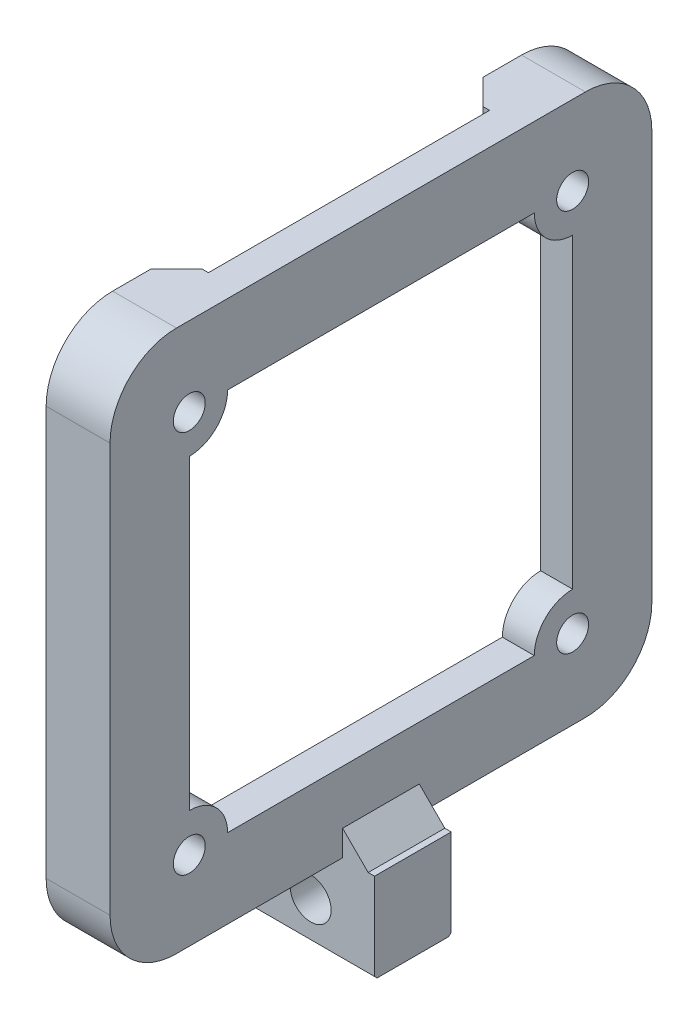
SolidWorks part; units mm, degrees
ref_plane "Front Plane" through (0, 0, 0) normal (0, 0, 1) x (1, 0, 0)
ref_plane "Top Plane" through (0, 0, 0) normal (0, 1, 0) x (1, 0, 0)
ref_plane "Right Plane" through (0, 0, 0) normal (1, 0, 0) x (0, 0, -1)
sketch "Sketch1" plane through (0, 0, 0) normal (1, 0, 0) x (0, 0, -1)
  line L0 (-23.0849, 19.7931) -> (-23.0849, -12.2069)
  line L1 (-20.0849, -15.2069) -> (11.9151, -15.2069)
  line L2 (14.9151, -12.2069) -> (14.9151, 19.7931)
  line L3 (11.9151, 22.7931) -> (-20.0849, 22.7931)
  line L4 (-19.0849, 15.7931) -> (-19.0849, -8.2069)
  line L5 (-19.0849, -11.2069) -> (-17.8349, -11.2069) construction
  line L6 (10.9151, -11.2069) -> (10.9151, -9.9569) construction
  line L7 (10.9151, 18.7931) -> (9.6651, 18.7931) construction
  line L8 (-16.0849, 18.7931) -> (-17.8349, 18.7931) construction
  line L9 (-19.0849, 18.7931) -> (-19.0849, 17.5431) construction
  line L10 (-19.0849, 18.7931) -> (-19.0849, -11.2069) construction
  line L11 (-17.8349, 18.7931) -> (-19.0849, 18.7931) construction
  line L12 (10.9151, 18.7931) -> (-19.0849, 18.7931) construction
  line L13 (-19.0849, 17.5431) -> (-19.0849, 15.7931) construction
  line L14 (7.9151, 18.7931) -> (-16.0849, 18.7931)
  line L15 (9.6651, 18.7931) -> (7.9151, 18.7931) construction
  line L16 (10.9151, 17.5431) -> (10.9151, 18.7931) construction
  line L17 (10.9151, -8.2069) -> (10.9151, 15.7931)
  line L18 (10.9151, 15.7931) -> (10.9151, 17.5431) construction
  line L19 (10.9151, -11.2069) -> (10.9151, 18.7931) construction
  line L20 (10.9151, -9.9569) -> (10.9151, -8.2069) construction
  line L21 (9.6651, -11.2069) -> (10.9151, -11.2069) construction
  line L22 (-16.0849, -11.2069) -> (7.9151, -11.2069)
  line L23 (7.9151, -11.2069) -> (9.6651, -11.2069) construction
  line L24 (-19.0849, -11.2069) -> (10.9151, -11.2069) construction
  line L25 (-17.8349, -11.2069) -> (-16.0849, -11.2069) construction
  line L26 (-19.0849, -9.9569) -> (-19.0849, -11.2069) construction
  line L27 (-19.0849, -8.2069) -> (-19.0849, -9.9569) construction
  arc A0 (-17.8349, 18.7931) -> (-19.0849, 17.5431) centre (-19.0849, 18.7931) ccw
  circle A1 centre (10.9151, 18.7931) radius 1.25
  arc A2 (-20.0849, 22.7931) -> (-23.0849, 19.7931) centre (-20.0849, 19.7931) ccw
  arc A3 (-23.0849, -12.2069) -> (-20.0849, -15.2069) centre (-20.0849, -12.2069) ccw
  arc A4 (11.9151, -15.2069) -> (14.9151, -12.2069) centre (11.9151, -12.2069) ccw
  arc A5 (14.9151, 19.7931) -> (11.9151, 22.7931) centre (11.9151, 19.7931) ccw
  circle A6 centre (-19.0849, -11.2069) radius 1.25
  circle A7 centre (10.9151, -11.2069) radius 1.25
  arc A8 (-19.0849, -11.2069) -> (-19.0849, -11.2069) centre (-19.0849, -11.2069) ccw
  arc A9 (10.9151, -11.2069) -> (10.9151, -11.2069) centre (10.9151, -11.2069) ccw
  arc A10 (10.9151, 18.7931) -> (10.9151, 18.7931) centre (10.9151, 18.7931) ccw
  arc A11 (-19.0849, 18.7931) -> (-19.0849, 18.7931) centre (-19.0849, 18.7931) ccw
  arc A12 (-19.0849, 15.7931) -> (-16.0849, 18.7931) centre (-19.0849, 18.7931) ccw
  arc A13 (7.9151, 18.7931) -> (10.9151, 15.7931) centre (10.9151, 18.7931) ccw
  arc A14 (-16.0849, -11.2069) -> (-19.0849, -8.2069) centre (-19.0849, -11.2069) ccw
  arc A15 (10.9151, -8.2069) -> (7.9151, -11.2069) centre (10.9151, -11.2069) ccw
  arc A16 (-19.0849, 17.5431) -> (-17.8349, 18.7931) centre (-19.0849, 18.7931) ccw construction
  circle A17 centre (-19.0849, 18.7931) radius 1.25
  arc A18 (-19.0849, -8.2069) -> (-16.0849, -11.2069) centre (-19.0849, -11.2069) ccw construction
  arc A19 (7.9151, -11.2069) -> (10.9151, -8.2069) centre (10.9151, -11.2069) ccw construction
  arc A20 (10.9151, 15.7931) -> (7.9151, 18.7931) centre (10.9151, 18.7931) ccw construction
  arc A21 (-16.0849, 18.7931) -> (-19.0849, 15.7931) centre (-19.0849, 18.7931) ccw construction
  dimension "D1" = 2.5
  dimension "D2" = 3
  dimension "D11" = 6
  dimension "D3" = 10.9151
  dimension "D4" = 14.9151
  dimension "D5" = 19.0849
  dimension "D6" = 23.0849
  dimension "D7" = 18.7931
  dimension "D8" = 22.7931
  dimension "D9" = 11.2069
  dimension "D10" = 4
extrude "Boss-Extrude1" add sketch "Sketch1" along normal blind 2.5 contours L2 A5 L3 A2 L0 A3 L1 A4 A17 A0 A7 A6 A1 L17 A15 L22 A14 L4 A12 L14 A13 region at (0, 21.5344, 21.8262)
sketch "Sketch2" plane through (0, 0, 0) normal (-1, 0, 0) x (0, 0, 1)
  line L0 (-17.1151, 19.7931) -> (-17.1151, -12.2069)
  line L1 (-11.9151, -17.4069) -> (20.0849, -17.4069)
  line L2 (25.2849, -12.2069) -> (25.2849, 19.7931)
  line L3 (20.0849, 24.9931) -> (-11.9151, 24.9931)
  line L4 (-14.9151, 19.7931) -> (-14.9151, -12.2069)
  line L5 (-11.9151, -15.2069) -> (20.0849, -15.2069)
  line L6 (23.0849, -12.2069) -> (23.0849, 19.7931)
  line L7 (20.0849, 22.7931) -> (-11.9151, 22.7931)
  line L8 (-14.9151, 19.7931) -> (-14.9151, -12.2069)
  line L9 (-11.9151, -15.2069) -> (20.0849, -15.2069)
  line L10 (23.0849, -12.2069) -> (23.0849, 19.7931)
  line L11 (20.0849, 22.7931) -> (-11.9151, 22.7931)
  arc A0 (-17.1151, -12.2069) -> (-11.9151, -17.4069) centre (-11.9151, -12.2069) ccw
  arc A1 (20.0849, -17.4069) -> (25.2849, -12.2069) centre (20.0849, -12.2069) ccw
  arc A2 (25.2849, 19.7931) -> (20.0849, 24.9931) centre (20.0849, 19.7931) ccw
  arc A3 (-11.9151, 24.9931) -> (-17.1151, 19.7931) centre (-11.9151, 19.7931) ccw
  arc A4 (-14.9151, -12.2069) -> (-11.9151, -15.2069) centre (-11.9151, -12.2069) ccw
  arc A5 (20.0849, -15.2069) -> (23.0849, -12.2069) centre (20.0849, -12.2069) ccw
  arc A6 (23.0849, 19.7931) -> (20.0849, 22.7931) centre (20.0849, 19.7931) ccw
  arc A7 (-11.9151, 22.7931) -> (-14.9151, 19.7931) centre (-11.9151, 19.7931) ccw
  arc A8 (-14.9151, -12.2069) -> (-11.9151, -15.2069) centre (-11.9151, -12.2069) ccw
  arc A9 (20.0849, -15.2069) -> (23.0849, -12.2069) centre (20.0849, -12.2069) ccw
  arc A10 (23.0849, 19.7931) -> (20.0849, 22.7931) centre (20.0849, 19.7931) ccw
  arc A11 (-11.9151, 22.7931) -> (-14.9151, 19.7931) centre (-11.9151, 19.7931) ccw
  dimension "D1" = 0
  dimension "D2" = 2.2
extrude "Boss-Extrude2" add sketch "Sketch2" against normal blind 2.5
sketch "Sketch3" plane through (0, 0, 0) normal (-1, 0, 0) x (0, 0, 1)
  line L8 (-15.1151, 19.7931) -> (-15.1151, -12.2069)
  line L9 (-11.9151, -15.4069) -> (20.0849, -15.4069)
  line L10 (23.2849, -12.2069) -> (23.2849, 19.7931)
  line L11 (20.0849, 22.9931) -> (-11.9151, 22.9931)
  line L12 (-15.1151, 19.7931) -> (-15.1151, -12.2069)
  line L13 (-11.9151, -15.4069) -> (20.0849, -15.4069)
  line L14 (23.2849, -12.2069) -> (23.2849, 19.7931)
  line L15 (20.0849, 22.9931) -> (-11.9151, 22.9931)
  line L16 (-17.1151, 19.7931) -> (-17.1151, -12.2069)
  line L17 (-11.9151, -17.4069) -> (20.0849, -17.4069)
  line L18 (25.2849, -12.2069) -> (25.2849, 19.7931)
  line L19 (20.0849, 24.9931) -> (-11.9151, 24.9931)
  line L20 (-17.1151, 19.7931) -> (-17.1151, -12.2069)
  line L21 (-11.9151, -17.4069) -> (20.0849, -17.4069)
  line L22 (25.2849, -12.2069) -> (25.2849, 19.7931)
  line L23 (20.0849, 24.9931) -> (-11.9151, 24.9931)
  arc A8 (-11.9151, 22.9931) -> (-15.1151, 19.7931) centre (-11.9151, 19.7931) ccw
  arc A9 (-15.1151, -12.2069) -> (-11.9151, -15.4069) centre (-11.9151, -12.2069) ccw
  arc A10 (20.0849, -15.4069) -> (23.2849, -12.2069) centre (20.0849, -12.2069) ccw
  arc A11 (23.2849, 19.7931) -> (20.0849, 22.9931) centre (20.0849, 19.7931) ccw
  arc A12 (-11.9151, 22.9931) -> (-15.1151, 19.7931) centre (-11.9151, 19.7931) ccw
  arc A13 (-15.1151, -12.2069) -> (-11.9151, -15.4069) centre (-11.9151, -12.2069) ccw
  arc A14 (20.0849, -15.4069) -> (23.2849, -12.2069) centre (20.0849, -12.2069) ccw
  arc A15 (23.2849, 19.7931) -> (20.0849, 22.9931) centre (20.0849, 19.7931) ccw
  arc A16 (-11.9151, 24.9931) -> (-17.1151, 19.7931) centre (-11.9151, 19.7931) ccw
  arc A17 (-17.1151, -12.2069) -> (-11.9151, -17.4069) centre (-11.9151, -12.2069) ccw
  arc A18 (20.0849, -17.4069) -> (25.2849, -12.2069) centre (20.0849, -12.2069) ccw
  arc A19 (25.2849, 19.7931) -> (20.0849, 24.9931) centre (20.0849, 19.7931) ccw
  arc A20 (-11.9151, 24.9931) -> (-17.1151, 19.7931) centre (-11.9151, 19.7931) ccw
  arc A21 (-17.1151, -12.2069) -> (-11.9151, -17.4069) centre (-11.9151, -12.2069) ccw
  arc A22 (20.0849, -17.4069) -> (25.2849, -12.2069) centre (20.0849, -12.2069) ccw
  arc A23 (25.2849, 19.7931) -> (20.0849, 24.9931) centre (20.0849, 19.7931) ccw
  dimension "D1" = 2
  dimension "D2" = 0
extrude "Boss-Extrude4" add sketch "Sketch3" along normal blind 2.5
sketch "Sketch5" plane through (0, -17.4069, 0) normal (0, -1, 0) x (1, 0, 0)
  line L0 (2.5, 20.0849) -> (-2.5, 20.0849) construction
  line L1 (-5, 7.0849) -> (5, 7.0849)
  line L2 (-5, 7.0849) -> (-5, 1.0849)
  line L3 (-5, 1.0849) -> (5, 1.0849)
  line L4 (5, 7.0849) -> (5, 1.0849)
  line L5 (-5, 7.0849) -> (5, 1.0849) construction
  line L6 (-5, 1.0849) -> (5, 7.0849) construction
  line L7 (2.5, -11.9151) -> (2.5, 20.0849) construction
  point P4 (0, 4.0849)
  point P8 (0, 20.0849)
  point P11 (2.5, 4.0849)
  dimension "D1" = 10
  dimension "D2" = 6
extrude "Boss-Extrude6" add sketch "Sketch5" along normal blind 8
chamfer "Chamfer1" distance 2 angle 45 2 edges at (-2.5, -17.4069, 4.0849) (2.5, -17.4069, 4.0849)
sketch "Sketch6" plane through (0, 0, 1.0849) normal (0, 0, -1) x (-1, 0, 0)
  line L0 (2.5, -17.4069) -> (-2.5, -17.4069) construction
  line L1 (5, -25.4069) -> (-5, -25.4069) construction
  circle A0 centre (0, -21.4069) radius 1.6
  point P5 (0, -17.4069)
  dimension "D1" = 3.2
  dimension "D2" = 4
extrude "Cut-Extrude1" cut sketch "Sketch6" against normal blind 8
chamfer "Chamfer2" distance 1 angle 45 2 edges at (5, -25.4069, 4.0849) (-5, -25.4069, 4.0849)
chamfer "Chamfer3" distance 1.2 angle 45 2 edges at (0, -25.4069, 1.0849) (0, -25.4069, 7.0849)
sketch "Sketch7" plane through (0, 22.9931, 0) normal (0, -1, 0) x (1, 0, 0)
  line L0 (-2.5, 15.0849) -> (0, 15.0849)
  line L1 (-2.5, -6.9151) -> (0, -6.9151)
  line L4 (0, -11.9151) -> (0, 20.0849)
  line L5 (0, 20.0849) -> (-2.5, 20.0849)
  line L6 (-2.5, 20.0849) -> (-2.5, -11.9151)
  line L7 (-2.5, -11.9151) -> (0, -11.9151)
  line L8 (0, -11.9151) -> (0, 20.0849)
  line L9 (0, 20.0849) -> (-2.5, 20.0849)
  line L10 (-2.5, 20.0849) -> (-2.5, -11.9151)
  line L11 (-2.5, -11.9151) -> (0, -11.9151)
  line M7 (0, -11.9151) -> (0, 20.0849)
  line M9 (-2.5, 20.0849) -> (-2.5, -11.9151)
  dimension "D2" = 5
  dimension "D3" = 5
  dimension "D1" = 0
extrude "Cut-Extrude2" cut sketch "Sketch7" against normal through all contours L1 L0 M9 M7 region at (-1.25, 22.9931, 4.0849)
chamfer "Chamfer4" distance 2 angle 45 2 edges at (-2.5, 23.9931, -6.9151) (-2.5, 23.9931, 15.0849)
